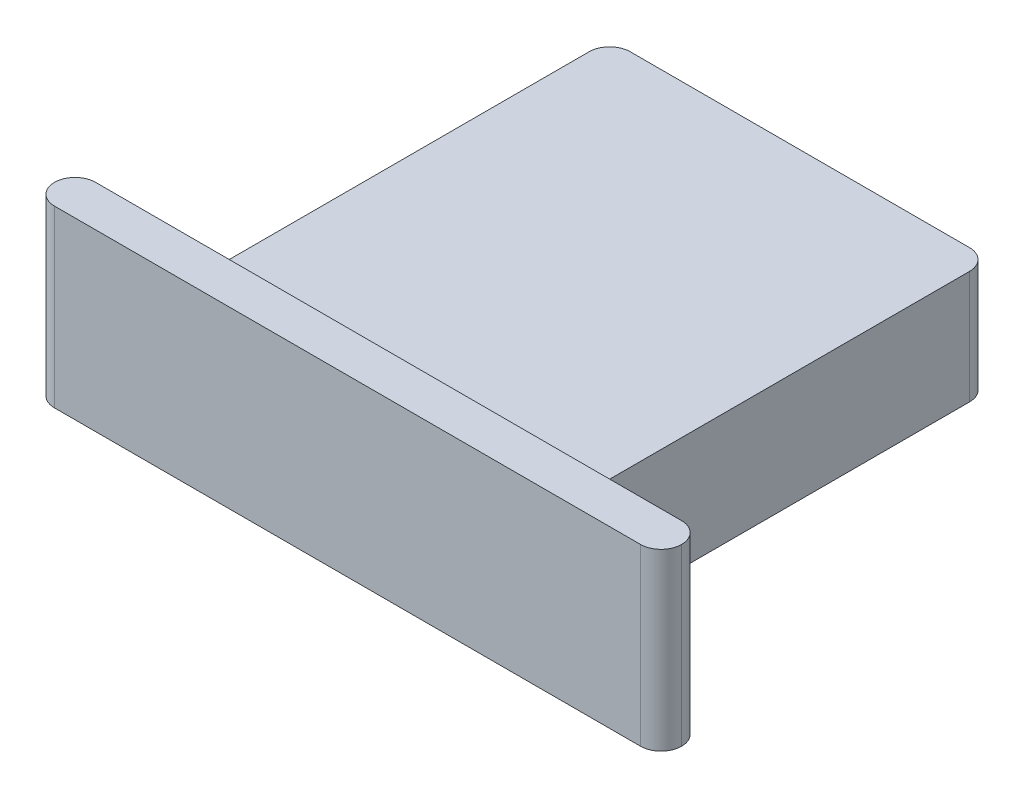
SolidWorks part; units mm, degrees
ref_plane "Alzado" through (0, 0, 0) normal (0, 0, 1) x (1, 0, 0)
ref_plane "Planta" through (0, 0, 0) normal (0, 1, 0) x (1, 0, 0)
ref_plane "Vista lateral" through (0, 0, 0) normal (1, 0, 0) x (0, 0, -1)
sketch "Croquis1" plane through (0, 0, 0) normal (0, 0, 1) x (1, 0, 0)
  line L1 (9.25, -2.75) -> (-9.25, -2.75)
  line L2 (9.25, -2.75) -> (9.25, 2.75)
  line L3 (9.25, 2.75) -> (-9.25, 2.75)
  line L4 (-9.25, -2.75) -> (-9.25, 2.75)
  line L5 (9.25, -2.75) -> (-9.25, 2.75) construction
  line L6 (9.25, 2.75) -> (-9.25, -2.75) construction
  point P0 (0, 0)
  dimension "D1" = 18.5
  dimension "D2" = 5.5
extrude "Saliente-Extruir1" add sketch "Croquis1" along normal blind 20 contours L3 L4 L1 L2
sketch "Croquis4" plane through (0, -2.75, 0) normal (0, -1, 0) x (1, 0, 0)
  line L0 (9.25, 20) -> (-9.25, 20) construction
  circle A0 centre (0, 11.5) radius 7
  dimension "D1" = 14
  dimension "D2" = 8.5
extrude "Cortar-Extruir1" cut sketch "Croquis4" against normal blind 1
sketch "Croquis5" plane through (0, 0, 20) normal (0, 0, 1) x (1, 0, 0)
  line L0 (9.25, 2.75) -> (-9.25, 2.75) construction
  line L1 (-15.25, -4.25) -> (15.25, -4.25)
  line L2 (-15.25, -4.25) -> (-15.25, 4.25)
  line L3 (-15.25, 4.25) -> (15.25, 4.25)
  line L4 (15.25, -4.25) -> (15.25, 4.25)
  line L5 (-15.25, -4.25) -> (15.25, 4.25) construction
  line L6 (-15.25, 4.25) -> (15.25, -4.25) construction
  point P0 (0, 0)
  dimension "D1" = 1.5
  dimension "D2" = 30.5
extrude "Saliente-Extruir2" add sketch "Croquis5" along normal blind 2 contours L1 L4 L3 L2
fillet "Redondeo2" radius 1 1 edges at (-15.25, 0, 22)
fillet "Redondeo3" radius 1 1 edges at (-15.25, 0, 20)
fillet "Redondeo4" radius 1 1 edges at (15.25, 0, 22)
fillet "Redondeo5" radius 1 1 edges at (15.25, 0, 20)
sketch "Croquis6" plane through (0, 0, 0) normal (0, 0, -1) x (-1, 0, 0)
  circle A0 centre (0, 0) radius 2
  dimension "D1" = 4
extrude "Cortar-Extruir2" cut sketch "Croquis6" against normal blind 4
fillet "Redondeo6" radius 1 1 edges at (-9.25, 0, 0)
fillet "Redondeo7" radius 1 1 edges at (9.25, 0, 0)
